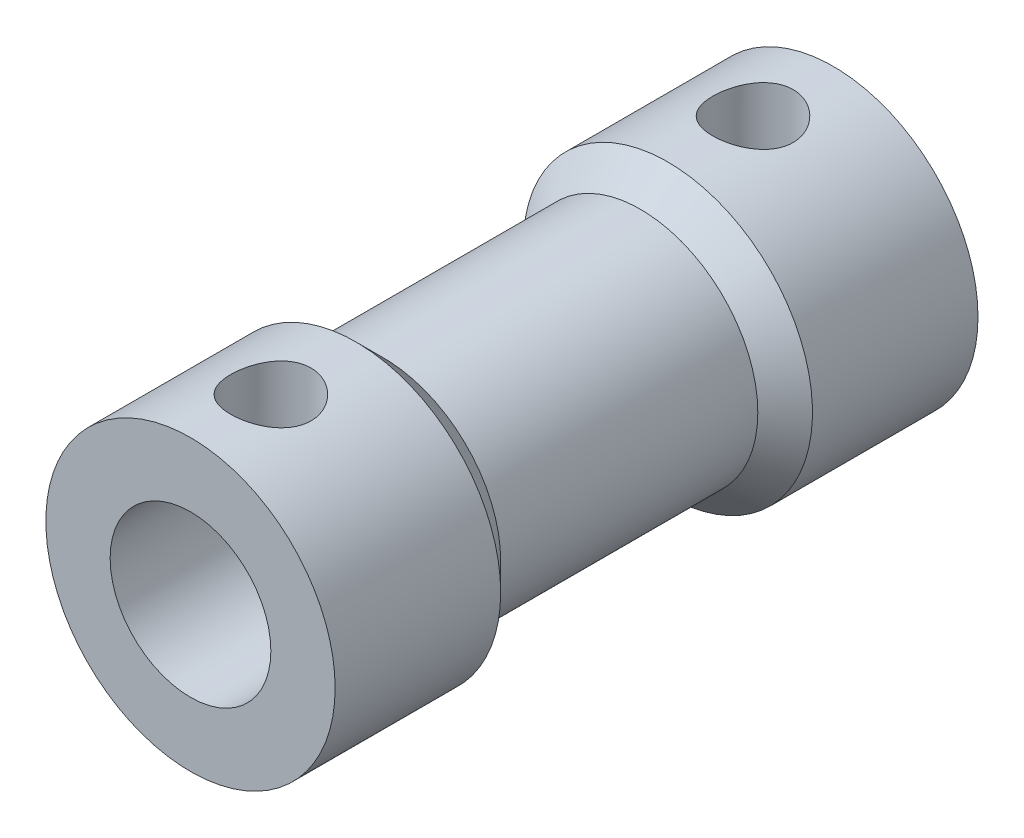
SolidWorks part; units mm, degrees
ref_plane "前基準面" through (0, 0, 0) normal (0, 0, 1) x (1, 0, 0)
ref_plane "上基準面" through (0, 0, 0) normal (0, 1, 0) x (1, 0, 0)
ref_plane "右基準面" through (0, 0, 0) normal (1, 0, 0) x (0, 0, -1)
ref_axis "基準軸1" through (0, -55, 0) along (0, 1, 0)
ref_axis "基準軸2" through (-88.99, 0, 0) along (1, 0, 0)
ref_axis "基準軸3" through (0, 0, 55) along (0, 0, -1)
sketch "草圖1" plane through (0, 0, 0) normal (0, 0, 1) x (1, 0, 0)
  circle A0 centre (0, 0) radius 4.5
  dimension "D1" = 9
extrude "填料-伸長1" add sketch "草圖1" along normal blind 5
sketch "草圖2" plane through (0, 0, 5) normal (0, 0, 1) x (1, 0, 0)
  circle A0 centre (0, 0) radius 3.65
  dimension "D1" = 7.3
extrude "填料-伸長2" add sketch "草圖2" along normal blind 10
sketch "草圖3" plane through (0, 0, 15) normal (0, 0, 1) x (1, 0, 0)
  circle A0 centre (0, 0) radius 4.5
  dimension "D1" = 9
extrude "填料-伸長3" add sketch "草圖3" along normal blind 5
chamfer "導角2" distance 1 angle 45 1 edges at (3.65, 0, 5)
chamfer "導角3" distance 1 angle 45 1 edges at (3.65, 0, 15)
hole_wizard "Ø5.0 (5) 直徑孔1" positions "草圖4" profile "草圖5" hole size "Ø5.0" standard "Ansi Metric"
sketch "草圖4" plane through (0, 0, 20) normal (0, 0, 1) x (1, 0, 0)
  line L0 (4.95, 0) -> (-4.95, 0) construction
  line L1 (0, -4.95) -> (0, 4.95) construction
  point P0 (0, 0)
  dimension "D1" = 0
  dimension "D2" = 0
sketch "草圖5" plane through (0, 0, 20) normal (1, 0, 0) x (0, -1, 0)
  line L0 (0, 0) -> (0, 6.5022)
  line L1 (0, 6.5022) -> (2.5, 5)
  line L2 (2.5, 5) -> (2.5, 0)
  line L5 (2.5, 0) -> (0, 0)
  line L10 (0, 6.5022) -> (-2.5, 5) construction
  line L11 (0, -6.35) -> (0, 107.95) construction
  dimension "苝ふ 畖" = 5
  dimension "苝ふ瞏 " = 5
  dimension "旧繷à " = 118
hole_wizard "Ø3.0 (3) 直徑孔1" positions "草圖6" profile "草圖7" hole size "Ø3.0" standard "Ansi Metric"
sketch "草圖6" plane through (0, 0, 0) normal (0, 0, -1) x (-1, 0, 0)
  line L0 (0, 4.95) -> (0, -4.95) construction
  line L1 (4.95, 0) -> (-4.95, 0) construction
  point P0 (0, 0)
  dimension "D1" = 0
  dimension "D2" = 0
sketch "草圖7" plane through (0, 0, 0) normal (1, 0, 0) x (0, 1, 0)
  line L0 (0, 0) -> (0, 5.9013)
  line L1 (0, 5.9013) -> (1.5, 5)
  line L2 (1.5, 5) -> (1.5, 0)
  line L5 (1.5, 0) -> (0, 0)
  line L10 (0, 5.9013) -> (-1.5, 5) construction
  line L11 (0, -6.35) -> (0, 107.95) construction
  dimension "苝ふ 畖" = 3
  dimension "苝ふ瞏 " = 5
  dimension "旧繷à " = 118
ref_plane "平面1" through (0, 4.5, 0) normal (0, 1, 0) x (1, 0, 0)
hole_wizard "M3x0.5  螺絲攻的螺孔鑽1" positions "草圖8" profile "草圖9" hole size "M3x0.5" standard "Ansi Metric" end condition up to next
sketch "草圖8" plane through (0, 4.5, 0) normal (0, 1, 0) x (1, 0, 0)
  line L0 (0, -4.95) -> (0, 4.95) construction
  line L1 (-4.95, 0) -> (4.95, 0) construction
  point P0 (0, -2.5)
  dimension "D1" = 0
  dimension "D2" = 2.5
sketch "草圖9" plane through (0, 4.5, 2.5) normal (1, 0, 0) x (0, 0, 1)
  line L0 (0, 0) -> (0, 9)
  line L1 (0, 9) -> (1.25, 9)
  line L2 (1.25, 9) -> (1.25, 0)
  line L5 (1.25, 0) -> (0, 0)
  line L11 (0, -6.35) -> (0, 107.95) construction
  dimension "砮 ふ 畖" = 2.5
  dimension "砮 ふ瞏 " = 9
ref_plane "平面2" through (0, 0, 10) normal (0, 0, -1) x (-1, 0, 0)
mirror "鏡射1" about plane through (0, 0, 10) normal (0, 0, -1) of "M3x0.5  螺絲攻的螺孔鑽1"
